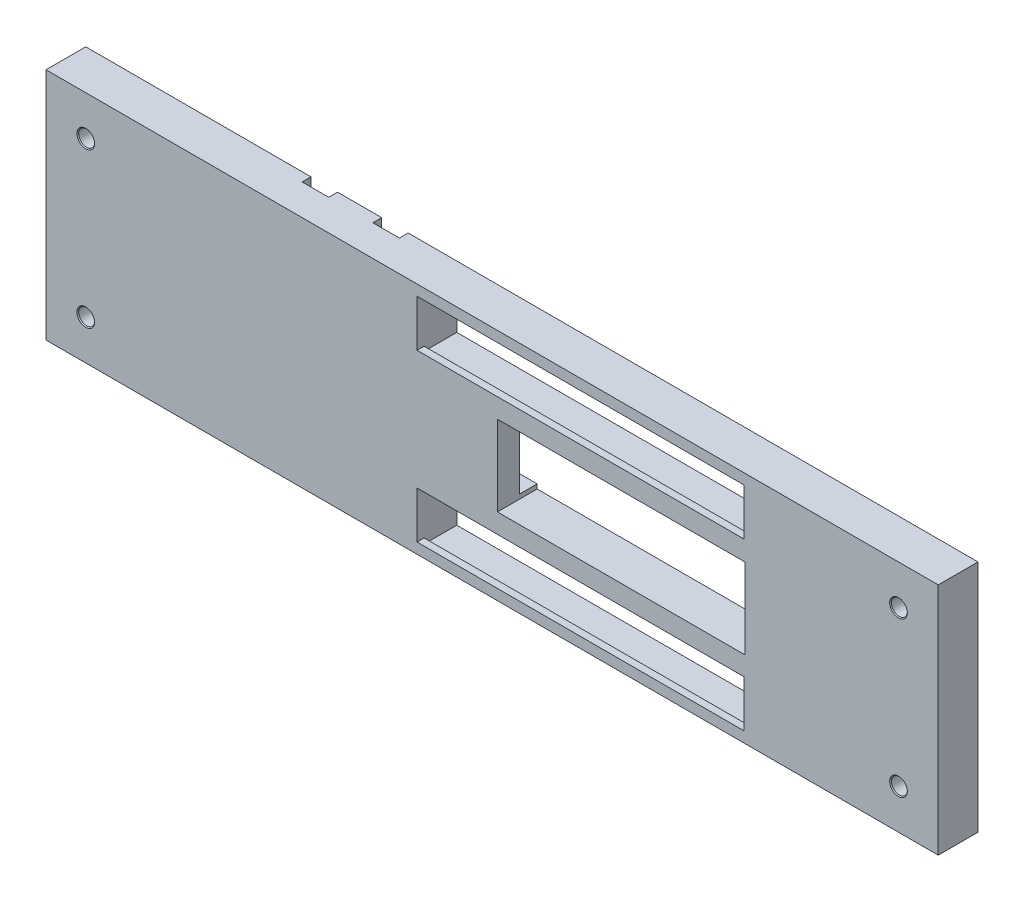
SolidWorks part; units mm, degrees
ref_plane "前视基准面" through (0, 0, 0) normal (0, 0, 1) x (1, 0, 0)
ref_plane "上视基准面" through (0, 0, 0) normal (0, 1, 0) x (1, 0, 0)
ref_plane "右视基准面" through (0, 0, 0) normal (1, 0, 0) x (0, 0, -1)
other "Configuration Table"
sketch "草图1" plane through (0, 0, 0) normal (0, 0, 1) x (1, 0, 0)
  line L1 (0, 0) -> (101, 0)
  line L2 (0, 0) -> (0, 26.5)
  line L3 (0, 26.5) -> (101, 26.5)
  line L4 (101, 0) -> (101, 26.5)
  dimension "D1" = 101
  dimension "D2" = 26.5
extrude "凸台-拉伸1" add sketch "草图1" along normal blind 2.5
sketch "草图7" plane through (0, 0, 0) normal (0, 0, 1) x (1, 0, 0)
  line L0 (0, 26.5) -> (4, 22.5)
  line L1 (0, 26.5) -> (4, 26.5)
  line L2 (0, 26.5) -> (0, 22.5)
  line L3 (0, 22.5) -> (4, 22.5)
  line L4 (4, 26.5) -> (4, 22.5)
  line L5 (0, 0) -> (4, 0)
  line L6 (0, 0) -> (0, 4)
  line L7 (0, 4) -> (4, 4)
  line L8 (4, 0) -> (4, 4)
  line L9 (101, 26.5) -> (97, 26.5)
  line L10 (101, 26.5) -> (101, 22.5)
  line L11 (101, 22.5) -> (97, 22.5)
  line L12 (97, 26.5) -> (97, 22.5)
  line L13 (101, 0) -> (97, 0)
  line L14 (101, 0) -> (101, 4)
  line L15 (101, 4) -> (97, 4)
  line L16 (97, 0) -> (97, 4)
  line L18 (97, 22.5) -> (101, 26.5)
  line L19 (97, 4) -> (101, 0)
  circle A0 centre (2, 24.5) radius 0.5974
  circle A1 centre (1.9156, 1.8995) radius 0.3791
  circle A2 centre (99, 24.5) radius 0.8607
  circle A3 centre (99, 2) radius 0.7914
  point P20 (97, 2)
  point P25 (2, 24.5)
  point P32 (4, 26.5)
  point P34 (4, 26.5)
  point P36 (4, 26.5)
  point P41 (1.9156, 1.8995)
  point P43 (1.9156, 1.8995)
  point P45 (1.9156, 1.8995)
  point P47 (1.9156, 1.8995)
  dimension "D1" = 4
  dimension "D2" = 4
  dimension "D3" = 4
  dimension "D4" = 4
  dimension "D5" = 4
  dimension "D6" = 4
  dimension "D7" = 4
  dimension "D8" = 2
sketch "草图10" plane through (0, 0, 2.5) normal (0, 0, 1) x (1, 0, 0)
  line L0 (101, 26.5) -> (0, 26.5) construction
  line L1 (42, 26.5) -> (79, 26.5)
  line L2 (42, 26.5) -> (42, 19.5)
  line L3 (42, 19.5) -> (79, 19.5)
  line L4 (79, 26.5) -> (79, 19.5)
  line L5 (0, 0) -> (101, 0) construction
  line L6 (42, 0) -> (79, 0)
  line L7 (42, 0) -> (42, 7)
  line L8 (42, 7) -> (79, 7)
  line L9 (79, 0) -> (79, 7)
  line L10 (101, 0) -> (101, 26.5) construction
  dimension "D1" = 22
  dimension "D2" = 22
  dimension "D3" = 37
  dimension "D4" = 37
  dimension "D5" = 7
  dimension "D6" = 7
extrude "切除-拉伸1" cut sketch "草图10" against normal blind 2.5
sketch "草图11" plane through (0, 0, 0) normal (0, 0, -1) x (-1, 0, 0)
  line L12 (-42, 26.5) -> (-42, 19.5)
  line L13 (-42, 19.5) -> (-79, 19.5)
  line L14 (-79, 19.5) -> (-79, 26.5)
  line L15 (-79, 26.5) -> (-101, 26.5)
  line L16 (-101, 26.5) -> (-101, 0)
  line L17 (-101, 0) -> (-79, 0)
  line L18 (-79, 0) -> (-79, 7)
  line L19 (-79, 7) -> (-42, 7)
  line L20 (-42, 7) -> (-42, 0)
  line L21 (-42, 0) -> (0, 0)
  line L22 (0, 0) -> (0, 26.5)
  line L23 (0, 26.5) -> (-42, 26.5)
  line L24 (-42, 26.5) -> (-42, 19.5)
  line L25 (-42, 19.5) -> (-79, 19.5)
  line L26 (-79, 19.5) -> (-79, 26.5)
  line L27 (-79, 26.5) -> (-101, 26.5)
  line L28 (-101, 26.5) -> (-101, 0)
  line L29 (-101, 0) -> (-79, 0)
  line L30 (-79, 0) -> (-79, 7)
  line L31 (-79, 7) -> (-42, 7)
  line L32 (-42, 7) -> (-42, 0)
  line L33 (-42, 0) -> (0, 0)
  line L34 (0, 0) -> (0, 26.5)
  line L35 (0, 26.5) -> (-42, 26.5)
  line L36 (-39.8, 24.3) -> (-39.8, 17.3)
  line L37 (-39.8, 17.3) -> (-81.2, 17.3)
  line L38 (-81.2, 17.3) -> (-81.2, 24.3)
  line L39 (-81.2, 24.3) -> (-98.8, 24.3)
  line L40 (-98.8, 24.3) -> (-98.8, 2.2)
  line L41 (-98.8, 2.2) -> (-81.2, 2.2)
  line L42 (-81.2, 2.2) -> (-81.2, 9.2)
  line L43 (-81.2, 9.2) -> (-39.8, 9.2)
  line L44 (-39.8, 9.2) -> (-39.8, 2.2)
  line L45 (-39.8, 2.2) -> (-2.2, 2.2)
  line L46 (-2.2, 2.2) -> (-2.2, 24.3)
  line L47 (-2.2, 24.3) -> (-39.8, 24.3)
  dimension "D1" = 0
  dimension "D3" = 2.2
extrude "凸台-拉伸2" add sketch "草图11" along normal blind 2
sketch "草图13" plane through (0, 0, 2.5) normal (0, 0, -1) x (-1, 0, 0)
  line L1 (-6.8, 6.8) -> (-2.2, 2.2)
  line L2 (-98.8, 24.3) -> (-94.2, 24.3)
  line L3 (-98.8, 24.3) -> (-98.8, 19.7)
  line L4 (-98.8, 19.7) -> (-94.2, 19.7)
  line L5 (-94.2, 24.3) -> (-94.2, 19.7)
  line L6 (-98.8, 2.2) -> (-94.2, 2.2)
  line L7 (-98.8, 2.2) -> (-98.8, 6.8)
  line L8 (-98.8, 6.8) -> (-94.2, 6.8)
  line L9 (-94.2, 2.2) -> (-94.2, 6.8)
  line L10 (-2.2, 24.3) -> (-6.8, 24.3)
  line L11 (-2.2, 24.3) -> (-2.2, 19.7)
  line L12 (-2.2, 19.7) -> (-6.8, 19.7)
  line L13 (-6.8, 24.3) -> (-6.8, 19.7)
  line L14 (-2.2, 2.2) -> (-6.8, 2.2)
  line L15 (-2.2, 2.2) -> (-2.2, 6.8)
  line L16 (-2.2, 6.8) -> (-6.8, 6.8)
  line L17 (-6.8, 2.2) -> (-6.8, 6.8)
  line L18 (-6.8, 19.7) -> (-2.5224, 23.9776)
  line L21 (-98.8, 24.3) -> (-94.2, 19.7)
  line L22 (-98.8, 2.2) -> (-94.2, 6.8)
  line L23 (-6.8, 24.3) -> (-2.2, 19.7)
  line L25 (-98.8, 24.3) -> (-98.8, 2.2) construction
  line L26 (-81.2, 24.3) -> (-98.8, 24.3) construction
  line L27 (-98.8, 2.2) -> (-81.2, 2.2) construction
  line L28 (-39.8, 2.2) -> (-2.2, 2.2) construction
  line L29 (-2.2, 2.2) -> (-2.2, 24.3) construction
  line L32 (-2.2, 24.3) -> (-39.8, 24.3) construction
  point P26 (-96.5, 22)
  point P28 (-96.5, 4.5)
  point P30 (-4.5, 22)
  point P32 (-4.5, 4.5)
  dimension "D1" = 4.6
  dimension "D2" = 4.6
  dimension "D3" = 4.6
  dimension "D4" = 4.6
  dimension "D5" = 4.6
  dimension "D6" = 4.6
  dimension "D7" = 4.6
  dimension "D8" = 4.6
  dimension "D9" = 0
hole_wizard "M6 开槽半沉头螺钉的锥形沉头孔4" positions "草图13" profile "草图16" countersink size "M6" standard "GB" end condition through all
sketch "草图16" plane through (4.5, 4.5, 2.5) normal (1, 0, 0) x (0, -1, 0)
  line L0 (0, 0) -> (0, 4.5)
  line L1 (0, 4.5) -> (0.9, 4.5)
  line L2 (0.9, 4.5) -> (0.9, 0.1)
  line L3 (0.9, 0.1) -> (1, 0)
  line L5 (1, 0) -> (0, 0)
  line L6 (-0.9, 0.1) -> (-1, 0) construction
  line L11 (0, -6.35) -> (0, 107.95) construction
  dimension "通孔孔直径" = 1.8
  dimension "通孔孔深度" = 4.5
  dimension "近端锥形沉头孔直径" = 2
  dimension "近端锥形沉头孔角度" = 90
sketch "草图17" plane through (0, 0, 0) normal (0, 0, -1) x (-1, 0, 0)
  line L12 (-94.8, 24.3) -> (-94.8, 20.3)
  line L20 (-94.8, 24.3) -> (-98.8, 24.3)
  line L22 (-98.8, 24.3) -> (-98.8, 20.3)
  line L44 (-94.8, 20.3) -> (-98.8, 20.3)
  line L46 (-94.8, 6.2) -> (-94.8, 2.2)
  line L47 (-2.2, 24.3) -> (-6.2, 24.3)
  line L48 (-2.2, 24.3) -> (-2.2, 20.3)
  line L49 (-2.2, 20.3) -> (-6.2, 20.3)
  line L50 (-6.2, 24.3) -> (-6.2, 20.3)
  line L51 (-94.8, 6.2) -> (-98.8, 6.2)
  line L52 (-98.8, 6.2) -> (-98.8, 2.2)
  line L53 (-94.8, 2.2) -> (-98.8, 2.2)
  line L54 (-2.2, 6.2) -> (-2.2, 2.2)
  line L55 (-2.2, 6.2) -> (-6.2, 6.2)
  line L56 (-6.2, 6.2) -> (-6.2, 2.2)
  line L57 (-2.2, 2.2) -> (-6.2, 2.2)
  circle A0 centre (-4.5, 4.5) radius 0.9 construction
  circle A1 centre (-4.5, 22) radius 0.9 construction
  circle A2 centre (-96.5, 4.5) radius 0.9 construction
  circle A3 centre (-96.5, 22) radius 0.9 construction
  circle A4 centre (-4.5, 4.5) radius 0.9
  circle A5 centre (-4.5, 22) radius 0.9
  circle A6 centre (-96.5, 4.5) radius 0.9
  circle A7 centre (-96.5, 22) radius 0.9
  circle M23 centre (-96.5, 22) radius 0.9
  circle M24 centre (-96.5, 4.5) radius 0.9
  circle M25 centre (-4.5, 22) radius 0.9
  circle M26 centre (-4.5, 4.5) radius 0.9
  line M43 (-2.2, 24.3) -> (-39.8, 24.3)
  line M48 (-98.8, 24.3) -> (-98.8, 2.2)
  line M49 (-98.8, 2.2) -> (-81.2, 2.2)
  line M53 (-39.8, 2.2) -> (-2.2, 2.2)
  line M54 (-2.2, 2.2) -> (-2.2, 24.3)
  dimension "D2" = 2
  dimension "D6" = 4
  dimension "D7" = 4
  dimension "D1" = 2
extrude "凸台-拉伸3" add sketch "草图17" along normal up to surface (2 mm away) contours M53 M54 M26 | M54 M43 M25 | M48 M23 | M48 M49 M24 region at (96.8, 6.1434, 0) region at (94.8566, 22.3, 0) region at (2.2566, 22.3, 0) region at (2.2566, 4.2, 0) up to face at (57.1667, 13.25, -2)
sketch "草图18" plane through (0, 0, 2.5) normal (0, 0, 1) x (1, 0, 0)
  line L0 (42, 19.5) -> (79, 19.5) construction
  line L1 (37, 17.8) -> (79.1, 17.8)
  line L2 (37, 17.8) -> (37, 8.7)
  line L3 (37, 8.7) -> (79.1, 8.7)
  line L4 (79.1, 17.8) -> (79.1, 8.7)
  line L5 (79, 7) -> (42, 7) construction
  line L6 (42, 26.5) -> (42, 19.5) construction
  line L7 (79, 0) -> (79, 7) construction
  line L8 (42, 7) -> (42, 0) construction
  line L9 (32, 19.5) -> (37, 19.5)
  line L10 (32, 19.5) -> (32, 7)
  line L11 (32, 7) -> (37, 7)
  line L12 (37, 19.5) -> (37, 7)
  line L13 (79.1, 19.5) -> (84.1, 19.5)
  line L14 (79.1, 19.5) -> (79.1, 7)
  line L15 (79.1, 7) -> (84.1, 7)
  line L16 (84.1, 19.5) -> (84.1, 7)
  dimension "D1" = 1.7
  dimension "D2" = 1.7
  dimension "D3" = 5
  dimension "D4" = 0.1
  dimension "D5" = 5
  dimension "D6" = 0
  dimension "D7" = 0
  dimension "D8" = 0
  dimension "D9" = 5
  dimension "D10" = 5
  dimension "D11" = 0
  dimension "D12" = 0
extrude "切除-拉伸2" cut sketch "草图18" against normal blind 1 contours L12 L9 L10 L11 L2 | L4 L1 L2 L3 | L16 L13 L14 L4 L15 region at (58.05, 13.25, 2.5) region at (34.5, 13.25, 2.5) region at (81.6, 13.25, 2.5)
sketch "草图20" plane through (0, 0, 1.5) normal (0, 0, 1) x (1, 0, 0)
  line L1 (51.1, 17.8) -> (79.1, 17.8)
  line L3 (51.1, 8.7) -> (79.1, 8.7)
  line L4 (79.1, 17.8) -> (79.1, 8.7)
  line L5 (79.1, 17.8) -> (51.1, 17.8)
  line L6 (79.1, 17.8) -> (79.1, 8.7)
  line L7 (79.1, 8.7) -> (51.1, 8.7)
  line L8 (51.1, 17.8) -> (51.1, 8.7)
  line L12 (37, 17.8) -> (37, 19.5)
  line L13 (37, 19.5) -> (32, 19.5)
  line L14 (32, 19.5) -> (32, 7)
  line L15 (32, 7) -> (37, 7)
  line L16 (37, 7) -> (37, 8.7)
  line L17 (37, 8.7) -> (79.1, 8.7)
  line L22 (79.1, 19.5) -> (79.1, 17.8)
  line L23 (79.1, 17.8) -> (37, 17.8)
  line L29 (51.1, 8.7) -> (79.1, 8.7)
  line L35 (79.1, 17.8) -> (51.1, 17.8)
  line L36 (79.1, 8.7) -> (79.1, 7)
  line L37 (79.1, 7) -> (84.1, 7)
  line L38 (84.1, 7) -> (84.1, 19.5)
  line L39 (84.1, 19.5) -> (79.1, 19.5)
  line M18 (37, 8.7) -> (79.1, 8.7)
  line M24 (79.1, 17.8) -> (37, 17.8)
  dimension "D2" = 28
  dimension "D1" = 0
extrude "切除-拉伸3" cut sketch "草图20" against normal up to next contours L4 M24 M18 region at (65.1, 13.25, 1.5)
sketch "草图22" plane through (79, 0, 0) normal (-1, 0, 0) x (0, 0, 1)
  line L0 (2.5, 0) -> (2.5, 7) construction
  line L1 (-2, 0) -> (2.5, 0)
  line L2 (-2, 0) -> (-2, 0.6)
  line L3 (-2, 0.6) -> (1.7, 0.6)
  line L4 (2.5, 0) -> (2.5, 1.146)
  line L5 (0, 13.25) -> (1.5, 13.25)
  line L7 (2.5, 1.146) -> (2.5, 1.2)
  line L8 (2.5, 1.2) -> (1.7, 1.2)
  line L9 (1.7, 0.6) -> (1.7, 1.2)
  line L10 (2.5, 7) -> (1.7, 7)
  line L11 (2.5, 7) -> (2.5, 6.5)
  line L12 (2.5, 6.5) -> (1.7, 6.5)
  line L13 (1.7, 7) -> (1.7, 6.5)
  line L14 (1.5, 13.25) -> (2.8388, 13.25)
  line L15 (0, 17.3) -> (1.5, 17.8)
  line L16 (1.7, 19.5) -> (1.7, 20)
  line L17 (0, 17.3) -> (0, 9.2)
  line L18 (-2, 8.7) -> (1.5, 8.7)
  line L19 (1.5, 8.7) -> (1.5, 17.8)
  line L20 (1.5, 17.8) -> (-2, 17.8)
  line L22 (-2, 8.7) -> (1.5, 8.7)
  line L24 (1.5, 17.8) -> (-2, 17.8)
  line L25 (2.5, 20) -> (1.7, 20)
  line L26 (2.5, 19.5) -> (2.5, 20)
  line L27 (2.5, 19.5) -> (1.7, 19.5)
  line L28 (1.7, 25.9) -> (1.7, 25.3)
  line L29 (2.5, 25.3) -> (1.7, 25.3)
  line L30 (2.5, 25.354) -> (2.5, 25.3)
  line L31 (2.5, 26.5) -> (2.5, 25.354)
  line L32 (-2, 25.9) -> (1.7, 25.9)
  line L33 (-2, 26.5) -> (-2, 25.9)
  line L34 (-2, 26.5) -> (2.5, 26.5)
  line L43 (-2, 17.8) -> (-2, 17.3)
  line L44 (-2, 17.8) -> (-2, 17.3)
  line L45 (-2, 17.3) -> (0, 17.3)
  line L46 (-2, 17.3) -> (0, 17.3)
  line L47 (0, 9.2) -> (-2, 9.2)
  line L48 (0, 9.2) -> (-2, 9.2)
  line L49 (-2, 9.2) -> (-2, 8.7)
  line L50 (-2, 9.2) -> (-2, 8.7)
  line M15 (2.5, 0) -> (2.5, 7)
  line M16 (2.5, 7) -> (-2, 7)
  line M17 (-2, 7) -> (-2, 0)
  line M18 (-2, 0) -> (2.5, 0)
  dimension "D1" = 0.8
  dimension "D2" = 1.2
  dimension "D3" = 0.6
  dimension "D4" = 0.5
  dimension "D5" = 0
extrude "凸台-拉伸4" add sketch "草图22" along normal up to surface (37 mm away) contours L34 L33 L32 L28 L29 L30 L31 | L27 L26 L25 L16 | L13 L12 M16 M15 | L9 L3 L8 M17 M18 M15 region at (79, 0.3906, 0.5292) region at (79, 6.75, 2.1) region at (79, 19.75, 2.1) region at (79, 26.1094, 0.5292) up to face at (42, 23, 0.25)
sketch "草图23" plane through (0, 0, 1.5) normal (0, 0, 1) x (1, 0, 0)
  line L6 (79.1, 19.5) -> (79.1, 17.8)
  line L7 (79.1, 17.8) -> (79.1, 8.7)
  line L8 (51.1, 8.7) -> (51.1, 17.8)
  line L9 (51.1, 17.8) -> (37, 17.8)
  line L10 (37, 17.8) -> (37, 19.5)
  line L11 (37, 19.5) -> (32, 19.5)
  line L12 (32, 19.5) -> (32, 7)
  line L13 (32, 7) -> (37, 7)
  line L14 (37, 7) -> (37, 8.7)
  line L15 (37, 8.7) -> (51.1, 8.7)
  line L16 (51.1, 8.7) -> (51.1, 17.8)
  line L17 (51.1, 17.8) -> (37, 17.8)
  line L18 (37, 17.8) -> (37, 19.5)
  line L19 (37, 19.5) -> (32, 19.5)
  line L20 (32, 19.5) -> (32, 7)
  line L21 (32, 7) -> (37, 7)
  line L22 (37, 7) -> (37, 8.7)
  line L23 (37, 8.7) -> (51.1, 8.7)
  line L24 (79.1, 8.7) -> (79.1, 7)
  line L25 (79.1, 7) -> (84.1, 7)
  line L26 (84.1, 7) -> (84.1, 19.5)
  line L27 (84.1, 19.5) -> (79.1, 19.5)
  line L28 (79.1, 19.5) -> (79.1, 17.8)
  line L29 (79.1, 17.8) -> (79.1, 8.7)
  line L30 (79.1, 8.7) -> (79.1, 7)
  line L31 (79.1, 7) -> (84.1, 7)
  line L32 (84.1, 7) -> (84.1, 19.5)
  line L33 (84.1, 19.5) -> (79.1, 19.5)
  line M15 (51.1, 8.7) -> (51.1, 17.8)
  line M16 (51.1, 17.8) -> (37, 17.8)
  line M17 (37, 17.8) -> (37, 19.5)
  line M18 (37, 19.5) -> (32, 19.5)
  line M19 (32, 19.5) -> (32, 7)
  line M20 (32, 7) -> (37, 7)
  line M21 (37, 7) -> (37, 8.7)
  line M22 (37, 8.7) -> (51.1, 8.7)
  dimension "D1" = 0
  dimension "D2" = 0
extrude "凸台-拉伸5" add sketch "草图23" along normal up to surface (1 mm away) contours M22 M15 M16 M17 M18 M19 M20 M21 | L32 L33 L28 L29 L30 L31 | L16 L17 L18 L19 L20 L21 L22 L23 region at (81.6, 13.25, 1.5) region at (40.9219, 13.25, 1.5) up to face at (60.5, 3.85, 2.5)
sketch "草图24" plane through (0, 0, 0) normal (0, -1, 0) x (1, 0, 0)
  line L0 (101, -2) -> (0, -2) construction
  line L1 (6.25, -2) -> (16.25, -2)
  line L2 (6.25, -2) -> (6.25, 0.5)
  line L3 (6.25, 0.5) -> (16.25, 0.5)
  line L4 (16.25, -2) -> (16.25, 0.5)
  line L5 (0, 2.5) -> (0, -2) construction
  line L7 (18.25, -2) -> (21.25, -2)
  line L8 (18.25, -2) -> (18.25, -1)
  line L9 (18.25, -1) -> (21.25, -1)
  line L10 (21.25, -2) -> (21.25, -1)
  line L11 (26.25, -2) -> (29.25, -2)
  line L12 (26.25, -2) -> (26.25, -1)
  line L13 (26.25, -1) -> (29.25, -1)
  line L14 (29.25, -2) -> (29.25, -1)
  line L15 (34.25, -2) -> (37.25, -2)
  line L16 (34.25, -2) -> (34.25, -1)
  line L17 (34.25, -1) -> (37.25, -1)
  line L18 (37.25, -2) -> (37.25, -1)
  dimension "D1" = 2.5
  dimension "D2" = 10
  dimension "D3" = 6.25
  dimension "D4" = 2
  dimension "D5" = 3
  dimension "D6" = 1
  dimension "D7" = 5
  dimension "D8" = 3
  dimension "D9" = 1
  dimension "D10" = 1
  dimension "D11" = 3
  dimension "D12" = 5
extrude "切除-拉伸4" cut sketch "草图24" against normal blind 15
chamfer "倒角1" distance 2 angle 45 3 edges at (16.25, 0, -0.75) (11.25, 0, 0.5) (6.25, 0, -0.75)
sketch "草图25" plane through (0, 26.5, 0) normal (0, 1, 0) x (1, 0, 0)
  line L0 (0, 2) -> (101, 2) construction
  line L1 (25.5, 2) -> (28.5, 2)
  line L2 (25.5, 2) -> (25.5, 1)
  line L3 (25.5, 1) -> (28.5, 1)
  line L4 (28.5, 2) -> (28.5, 1)
  line L5 (0, -2.5) -> (0, 2) construction
  line L11 (33.5, 1) -> (36.5, 1)
  line L12 (33.5, 1) -> (33.5, 2)
  line L13 (33.5, 2) -> (36.5, 2)
  line L14 (36.5, 1) -> (36.5, 2)
  dimension "D1" = 25.5
  dimension "D2" = 3
  dimension "D3" = 1
  dimension "D4" = 5
  dimension "D5" = 3
  dimension "D6" = 1
extrude "切除-拉伸5" cut sketch "草图25" against normal up to next
